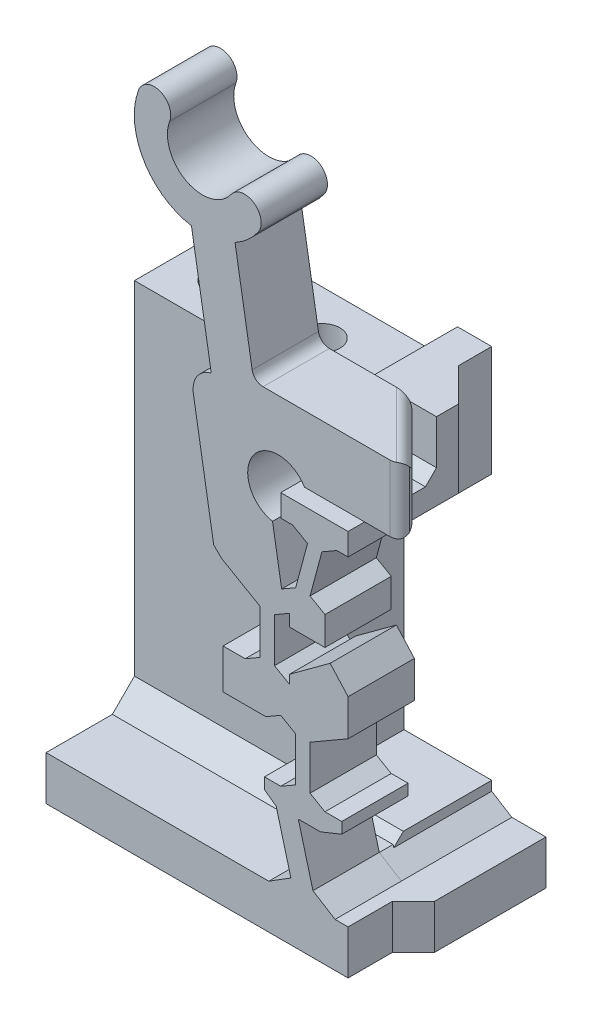
SolidWorks part; units mm, degrees
material "Nylon 6/12"
ref_plane "Front Plane" through (0, 0, 0) normal (0, 0, 1) x (1, 0, 0)
ref_plane "Top Plane" through (0, 0, 0) normal (0, 1, 0) x (1, 0, 0)
ref_plane "Right Plane" through (0, 0, 0) normal (1, 0, 0) x (0, 0, -1)
sketch "Sketch-SkeletonConfigUp" plane through (0, 0, 0) normal (0, 0, 1) x (1, 0, 0)
  line L0 (0, 0) -> (0, -50000) construction
  line L1 (0, 0) -> (4.5811, 6.2164) construction
  line L2 (9.8143, 13.3177) -> (4.5811, 13.945) construction
  line L3 (4.5811, 13.945) -> (2.9713, 10.4094) construction
  line L4 (2.9713, 10.4094) -> (4.5811, 6.2164) construction
  line L5 (4.5811, 13.945) -> (6.2429, 19.1409) construction
  line L6 (2.9713, 10.4094) -> (0.0405, 27.8193) construction
  line L7 (4.5811, 6.2164) -> (9.8143, 13.3177) construction
  line L8 (-587.3593, -797.0242) -> (9.8143, 13.3177) construction
  dimension "D2" = 7.7221
  dimension "D3" = 8.8212
  dimension "D4" = 5.2707
  dimension "D5" = 119.553
  dimension "D6" = 3.8848
  dimension "D7" = 5.4552
  dimension "D8" = 17.6549
  dimension "D9" = 4.4914
  dimension "D10" = 6.745
  dimension "D11" = 145.964
  dimension "D12" = 143.612
sketch "Sketch-SkeletonConfigDown" plane through (0, 0, 0) normal (0, 0, 1) x (1, 0, 0)
  line L0 (0, 0) -> (0, -50000) construction
  line L1 (0, 0) -> (4.5811, 6.2164) construction
  line L2 (9.8143, 13.3177) -> (4.5811, 13.945) construction
  line L3 (4.5811, 13.945) -> (6.1909, 10.4094) construction
  line L4 (6.1909, 10.4094) -> (4.5811, 6.2164) construction
  line L5 (4.5811, 13.945) -> (1.753, 18.6098) construction
  line L6 (6.1909, 10.4094) -> (-8.8652, 19.6294) construction
  line L7 (4.5811, 6.2164) -> (9.8143, 13.3177) construction
  line L8 (-589.9357, -800.5203) -> (9.8143, 13.3177) construction
  dimension "D2" = 7.7221
  dimension "D3" = 8.8212
  dimension "D4" = 5.2707
  dimension "D5" = 119.553
  dimension "D6" = 3.8848
  dimension "D7" = 5.4552
  dimension "D8" = 17.6549
  dimension "D9" = 4.4914
  dimension "D10" = 6.745
  dimension "D11" = 145.964
  dimension "D1" = 143.612
ref_plane "Plane-Cam Base" through (9.128, 0, 0) normal (1, 0, 0) x (0, 0, -1)
ref_plane "Plane-Down-to-Up Derailleur Clearance" through (6.628, 0, 0) normal (1, 0, 0) x (0, 0, -1)
ref_plane "Plane-Cam Cavity Roof" through (5.128, 0, 0) normal (1, 0, 0) x (0, 0, -1)
sketch "Sketch-SwitchBossUp" plane through (0, 0, 0) normal (0, 0, 1) x (1, 0, 0)
  line L0 (3.5811, 11.4759) -> (3.5811, 12.945) construction
  line L5 (5.5811, 12.5552) -> (5.5811, 11.263)
  line L7 (1.5115, 25.1048) -> (2.3566, 20.0847)
  line L8 (-0.4607, 24.7728) -> (0.4359, 19.4465)
  line L9 (2.9713, 10.4094) -> (0.0405, 27.8193) construction
  line L11 (-0.0396, 22.2712) -> (1.9326, 22.6032) construction
  line L15 (6.628, -23.7286) -> (6.628, 23.7286) construction
  line L16 (2.9713, 10.4094) -> (4.5811, 6.2164) construction
  line L17 (3.5811, 12.945) -> (3.5811, 14.945) construction
  line L18 (5.5811, 12.945) -> (5.5811, 14.945) construction
  line L19 (4.2561, 13.945) -> (4.9061, 13.945) construction
  line L20 (3.5811, 14.945) -> (5.5811, 14.945) construction
  line L21 (3.5811, 12.945) -> (5.5811, 12.945) construction
  line L22 (4.5811, 12.945) -> (4.5811, 14.945) construction
  line L23 (4.5811, 6.2164) -> (8.5405, 7.1023) construction
  line L24 (1.9713, 9.4094) -> (1.9713, 11.4094) construction
  line L25 (3.9713, 9.4094) -> (3.9713, 11.4094) construction
  line L26 (3.9713, 9.4094) -> (1.9713, 9.4094) construction
  line L27 (1.9713, 11.4094) -> (3.9713, 11.4094) construction
  line L28 (3.5811, 7.2164) -> (5.5811, 7.2164) construction
  line L29 (3.5811, 7.2164) -> (3.5811, 5.2164) construction
  line L30 (5.5811, 7.2164) -> (5.5811, 5.2164) construction
  line L31 (3.5811, 5.2164) -> (5.5811, 5.2164) construction
  line L32 (4.9061, 6.2164) -> (4.2561, 6.2164) construction
  line L40 (3.2963, 10.4094) -> (2.6463, 10.4094) construction
  line L66 (0.0405, 27.8193) -> (0.0405, 50027.8193) construction
  line L74 (0.5455, 12.7717) -> (-0.3728, 18.2264)
  line L75 (0.3841, 13.7302) -> (2.3564, 14.0622) construction
  line L76 (5.5811, 11.263) -> (5.5811, 12.5552) construction
  line L77 (5.5811, 7.6061) -> (6.628, 8.2105)
  line L80 (5.8152, 10.763) -> (6.628, 9.8603)
  line L81 (9.128, 1033.2419) -> (9.128, 20.0586) construction
  line L82 (4.6532, 17.0847) -> (9.028, 17.0847)
  line L85 (6.9307, 9.5241) -> (8.5405, 7.7363) construction
  line L88 (5.7256, 16.3347) -> (6.628, 16.3347)
  line L92 (3.7762, 8.3129) -> (6.9307, 9.5241) construction
  line L95 (2.3566, 20.0847) -> (7.4359, 20.0847)
  line L96 (7.4359, 20.0847) -> (9.028, 20.0847)
  line L97 (3.2085, 15.0241) -> (3.6203, 12.5779)
  line L98 (1.9713, 9.0197) -> (0.9713, 9.0197)
  line L99 (0.9713, 9.0197) -> (0.9713, 7.2164)
  line L100 (0.9713, 7.2164) -> (2.9061, 7.2164)
  line L101 (4.5811, 6.2164) -> (6.9307, 9.5241) construction
  line L103 (0.0405, 27.8193) -> (1.9448, 26.4638) construction
  line L104 (6.9307, 9.5241) -> (8.5405, 7.7363) construction
  line L107 (1.9713, 9.4094) -> (1.9713, 9.0197) construction
  line L109 (0.0405, 27.8193) -> (-2.1498, 28.6358) construction
  line L111 (6.628, 9.8603) -> (6.628, 8.2105)
  line L112 (6.628, 9.8603) -> (6.9307, 9.5241) construction
  line L113 (2.8424, 4.8267) -> (2.8424, 4.3267)
  line L114 (7.3693, 7.7363) -> (7.3563, 7.7363) construction
  line L121 (5.0383, -1.1653) -> (5.0383, 1.4614) construction
  line L122 (2.8616, 17.0847) -> (3.2085, 15.0241) construction
  line L127 (5.5811, 15.3347) -> (5.5811, 14.945) construction
  line L130 (6.0388, 0.837) -> (6.628, 0.837)
  line L132 (2.8424, 4.3267) -> (3.3749, 3.937)
  line L133 (2.9713, 10.4094) -> (6.1909, 10.4094) construction
  line L134 (4.5811, 10.4094) -> (4.5811, 13.945) construction
  line L135 (4.5811, 10.4094) -> (4.5811, 6.2164) construction
  line L136 (0.8973, 12.4192) -> (0.5455, 12.7717)
  line L137 (3.9713, 9.4094) -> (5.5811, 7.2164) construction
  line L139 (5.8152, 10.763) -> (3.9713, 9.4094)
  line L141 (4.0386, 1.4604) -> (3.0388, 0.8347)
  line L142 (3.0388, 0.8347) -> (3.0388, -1.1653)
  line L143 (9.128, 20.0586) -> (9.128, 18.3333) construction
  line L145 (9.128, 16.6071) -> (9.128, -49992.4167) construction
  line L147 (5.5811, 11.263) -> (5.5811, 12.5552) construction
  line L150 (3.0388, -1.1653) -> (5.0383, -1.1653)
  line L151 (3.3749, 3.937) -> (4.3749, 3.937) construction
  line L152 (4.792, 14.945) -> (4.2561, 12.945)
  line L153 (5.442, 14.945) -> (4.9061, 12.945)
  line L157 (3.5811, 16.3347) -> (3.5811, 15.3347)
  line L158 (6.117, 15.3347) -> (6.628, 15.3347)
  line L162 (3.2963, 11.4094) -> (3.2963, 9.4094)
  line L164 (2.6463, 11.4094) -> (2.6463, 9.4094)
  line L169 (4.2561, 7.2164) -> (4.2561, 5.2164)
  line L170 (4.9061, 5.2164) -> (4.9061, 7.2164)
  line L175 (4.2561, 7.2164) -> (3.5811, 7.6061)
  line L176 (4.9061, 7.2164) -> (5.5811, 7.6061)
  line L177 (5.5811, 7.2164) -> (5.5811, 7.6061) construction
  line L179 (4.2561, 5.2164) -> (3.5811, 4.8267)
  line L180 (3.5811, 5.2164) -> (3.5811, 4.8267) construction
  line L181 (3.5811, 4.8267) -> (2.8424, 4.8267)
  line L183 (4.9061, 5.2164) -> (5.5811, 4.8267)
  line L184 (5.5811, 5.2164) -> (5.5811, 4.8267) construction
  line L186 (9.128, -23.7286) -> (9.128, 23.7286) construction
  line L187 (2.6463, 9.4094) -> (1.9713, 9.0197)
  line L188 (3.2963, 9.4094) -> (3.9713, 9.0197)
  line L189 (3.2963, 11.4094) -> (3.9713, 11.7991)
  line L190 (2.6463, 11.4094) -> (0.8973, 12.4192)
  line L191 (3.9713, 11.4094) -> (3.9713, 11.7991) construction
  line L192 (3.9713, 11.7991) -> (3.9713, 11.263)
  line L193 (4.9061, 12.945) -> (5.5811, 12.5552)
  line L194 (4.2561, 12.945) -> (3.6203, 12.5779)
  line L195 (3.9713, 11.263) -> (5.5811, 11.263)
  line L196 (3.9713, 9.4094) -> (3.9713, 9.0197)
  line L197 (3.5811, 7.2164) -> (3.5811, 7.6061) construction
  line L199 (3.5811, 7.6061) -> (2.9061, 7.2164)
  line L201 (2.8424, 4.3267) -> (2.8424, 3.937) construction
  line L202 (2.8424, 3.937) -> (3.3749, 3.937) construction
  line L204 (5.0383, 1.437) -> (3.0388, 1.437) construction
  line L205 (3.0388, 1.437) -> (3.0388, 0.8347) construction
  line L206 (5.0383, 1.4614) -> (6.0388, 0.837)
  line L207 (9.128, 18.3333) -> (9.128, 16.6071) construction
  line L208 (6.628, -1.1653) -> (6.628, 0.837)
  line L209 (9.128, 20.0586) -> (9.128, 16.6071) construction
  line L211 (5.0383, 1.4614) -> (4.3749, 3.937)
  line L212 (4.0386, 1.4604) -> (3.3749, 3.937)
  line L214 (4.792, 14.945) -> (4.1169, 15.3347)
  line L215 (4.1169, 15.3347) -> (3.5811, 15.3347)
  line L216 (5.442, 14.945) -> (6.117, 15.3347)
  line L217 (5.5811, 12.945) -> (5.5811, 12.5552) construction
  line L218 (5.442, 14.945) -> (5.442, 15.3347) construction
  line L219 (6.117, 15.3347) -> (4.1169, 15.3347) construction
  line L221 (9.028, 17.0847) -> (9.028, 20.0847)
  line L224 (3.5811, 16.3347) -> (5.7256, 16.3347)
  line L232 (6.628, 15.3347) -> (6.628, 16.3347)
  line L233 (6.628, -1.1653) -> (5.0383, -1.1653)
  line L240 (4.3749, 3.937) -> (5.3749, 3.937)
  line L241 (5.3749, 3.937) -> (6.3424, 4.3267)
  line L248 (2.8616, 17.0847) -> (4.6532, 17.0847) construction
  line L367 (5.5811, 4.8267) -> (6.3424, 4.8267)
  line L368 (6.3424, 4.8267) -> (6.3424, 4.3267)
  arc A0 (1.5115, 25.1048) -> (2.5558, 26.0289) centre (0.0405, 27.8193) ccw
  arc A1 (-0.4607, 24.7728) -> (-2.8525, 28.8978) centre (0.0405, 27.8193) cw
  arc A2 (-2.8525, 28.8978) -> (-1.447, 28.3738) centre (-2.1498, 28.6358) cw
  arc A3 (2.5558, 26.0289) -> (1.3338, 26.8987) centre (1.9448, 26.4638) ccw
  arc A4 (-1.447, 28.3738) -> (1.3338, 26.8987) centre (0.0405, 27.8193) ccw
  arc A5 (3.5811, 12.945) -> (3.5811, 14.945) centre (3.1778, 13.945) ccw construction
  arc A6 (5.5811, 12.945) -> (5.5811, 14.945) centre (5.9843, 13.945) cw construction
  arc A7 (2.5293, 9.921) -> (1.9713, 11.4094) centre (1.568, 10.4094) ccw construction
  arc A8 (3.9713, 11.4094) -> (3.9713, 9.4094) centre (4.3745, 10.4094) ccw construction
  arc A9 (3.5811, 7.2164) -> (3.5811, 5.2164) centre (3.1779, 6.2164) cw construction
  arc A10 (5.5811, 7.2164) -> (5.5811, 5.2164) centre (5.9844, 6.2164) ccw construction
  arc A19 (-0.3728, 18.2264) -> (0.4359, 19.4465) centre (0.6836, 18.4042) cw
  circle A28 centre (0.0405, 27.8193) radius 2.3375 construction
  arc A29 (1.9713, 9.4094) -> (2.5293, 9.921) centre (1.568, 10.4094) ccw construction
  arc A37 (3.2085, 15.0241) -> (4.6532, 17.0847) centre (3.4651, 16.381) cw
  point P53 (4.5811, 13.945)
  point P63 (2.9713, 10.4094)
  point P93 (0.9465, 22.4372)
  dimension "D23" = 1.5875
  dimension "D24" = 0.75
  dimension "D2" = 2
  dimension "D5" = 2
  dimension "D6" = 0.65
  dimension "D8" = 42
  dimension "D16" = 42
  dimension "D27" = 120
  dimension "D28" = 120
  dimension "D29" = 120
  dimension "D30" = 120
  dimension "D31" = 120
  dimension "D32" = 120
  dimension "D33" = 120
  dimension "D34" = 120
  dimension "D17" = 0.5
  dimension "D21" = 1
  dimension "D9" = 17.5
  dimension "D22" = 1
  dimension "D38" = 2
  dimension "D39" = 0.5
  dimension "D40" = 60
  dimension "D41" = 1
  dimension "D42" = 45
  dimension "D43" = 120
  dimension "D10" = 15
  dimension "D12" = 2.5
  dimension "D13" = 1
  dimension "D19" = 1
  dimension "D25" = 15
  dimension "D26" = 120
  dimension "D35" = 120
  dimension "D20" = 3
  dimension "D48" = 2
  dimension "D49" = 0.6
  dimension "D7" = 0.75
  dimension "D14" = 3
  dimension "D82" = 1
  dimension "D83" = 3.5
extrude "Boss-Switch Body" add sketch "Sketch-SwitchBossUp" along normal blind 3
sketch "Sketch1" plane through (0, 0, 0) normal (0, 0, -1) x (-1, 0, 0)
  line L1 (-7.5811, -1.1653) -> (0.4122, -1.1653)
  line L2 (-7.5811, -1.1653) -> (-7.5811, 0.837)
  line L4 (0.4122, -1.1653) -> (0.4122, 0.8347)
  line L5 (-3.5811, 18.8347) -> (-7.5811, 18.8347)
  line L10 (-7.5811, 18.8347) -> (-7.5811, 15.3347)
  line L11 (-4.0386, 1.4604) -> (-5.0386, 1.4604)
  line L12 (-7.5811, 15.3347) -> (-3.5811, 15.3347)
  line L13 (-4.0386, 1.4604) -> (-3.0388, 0.8347)
  line L14 (-3.5811, 15.3347) -> (-3.5811, 18.8347)
  line L20 (-4.3749, 3.937) -> (-5.0383, 1.4614) construction
  line L22 (-3.0388, -1.1653) -> (-6.628, -1.1653) construction
  line L23 (-3.0388, 0.8347) -> (0.4122, 0.8347)
  line L24 (-5.0386, 1.4604) -> (-6.0388, 0.837)
  line L25 (-6.0388, 0.837) -> (-7.5811, 0.837)
  point P5 (-3.5811, 15.3347)
  dimension "D1" = 3.5
extrude "Boss-Flange Width" add sketch "Sketch1" along normal blind 5
ref_plane "Plane-Sta2Sit Groove" through (0.0405, 0, 0) normal (1, 0, 0) x (0, 0, -1)
ref_plane "Plane-Cam Outer Surface" through (-12.0395, 0, 0) normal (1, 0, 0) x (0, 0, -1)
ref_plane "Plane-FlangeTop" through (-7.0395, 0, 0) normal (1, 0, 0) x (0, 0, -1)
sketch "Sketch2" plane through (-7.0395, 0, 0) normal (1, 0, 0) x (0, 0, -1)
  line L0 (5, 15.3347) -> (-3, 15.3347) construction
  line L1 (5, 17.3347) -> (1, 17.3347)
  line L2 (5, 17.3347) -> (5, 15.3347)
  line L3 (5, 15.3347) -> (1, 15.3347)
  line L4 (1, 17.3347) -> (1, 15.3347)
  line L5 (-3, -1.1653) -> (-3, 0.837) construction
  line L11 (5, 0.8347) -> (-3, 0.8347)
  line L12 (5, 0.8347) -> (5, -1.1653)
  line L13 (5, -1.1653) -> (-3, -1.1653)
  line L14 (-3, 0.8347) -> (-3, -1.1653)
  line L15 (0, 10.4094) -> (0, 27.8193) construction
  line L17 (5, 0.837) -> (5, -1.1653) construction
  line L18 (-3, 0.8347) -> (0, 0.8347) construction
  dimension "D1" = 1
  dimension "D2" = 2
extrude "Boss-Flange Height" add sketch "Sketch2" along normal up to surface (11.6675 mm away)
sketch "Sketch24" plane through (0, 0, 0) normal (0, 0, 1) x (1, 0, 0)
  line L0 (3.5811, 16.3347) -> (7.5811, 16.3347)
  line L1 (7.5811, 17.0847) -> (7.5811, 15.3347) construction
  line L2 (3.5811, 16.3347) -> (3.5811, 18.8347)
  line L3 (3.5811, 18.8347) -> (7.5811, 18.8347)
  line L4 (7.5811, 18.8347) -> (7.5811, 16.3347)
  point P5 (7.5811, 18.8347)
extrude "Cut-Wall Clearance" cut sketch "Sketch24" against normal up to surface (1 mm away) up to face at (-1.7292, 16.3347, -1)
sketch "Sketch10" plane through (0, 15.3347, 0) normal (0, 1, 0) x (1, 0, 0)
  line L0 (9.128, -23.7286) -> (9.128, 23.7286) construction
  line L1 (7.5811, 5) -> (5.128, 5)
  line L2 (7.5811, 5) -> (7.5811, 2)
  line L3 (7.5811, 2) -> (5.128, 2)
  line L5 (4.628, 7) -> (4.628, 1) construction
  line L6 (3.5811, 1) -> (-7.0395, 1) construction
  line L8 (5.128, 5) -> (5.128, 2)
  dimension "D1" = 1
  dimension "D2" = 0.5
  dimension "D3" = 4.5
extrude "Cut-Up-To-Down Derailleur Clearance" cut sketch "Sketch10" along normal up to next
sketch "Sketch17" plane through (0, 15.3347, 0) normal (0, -1, 0) x (1, 0, 0)
  line L0 (5.128, -5) -> (-7.0395, -5)
  line L1 (5.128, -5) -> (-7.0395, -5) construction
  line L2 (-7.0395, -5) -> (-7.0395, -1)
  line L3 (-7.0395, -1) -> (5.128, -1)
  line L4 (5.128, -1) -> (5.128, -5)
  line L5 (-7.0395, -1) -> (-7.0395, -5) construction
extrude "Boss-Flange Support" add sketch "Sketch17" along normal up to surface (14.5 mm away) up to face at (-2.0003, 0.8347, -1)
sketch "Sketch-HolePositions" plane through (0, -1.1653, 0) normal (0, -1, 0) x (1, 0, 0)
  line L0 (-7.0395, -3) -> (7.5811, -3) construction
  line L1 (7.5811, -5) -> (-7.0395, -5) construction
  line L2 (7.5811, -5) -> (7.5811, 0) construction
  line L4 (-7.0395, -22.2167) -> (-7.0395, 22.2167) construction
  point P6 (-5.0395, -3)
  point P7 (-0.5395, -3)
  dimension "D1" = 2
  dimension "D2" = 4.5
  dimension "D3" = 2
sketch "Sketch6" plane through (0, -1.1653, 0) normal (0, -1, 0) x (-1, 0, 0)
  point P0 (5.0395, 3)
  point P3 (0.5395, 3)
hole_wizard "Tap Drill for M2x0.4 Tap1" positions "Sketch6" profile "Sketch5" hole size "M2x0.4" standard "ANSI Metric" end condition through all
sketch "Sketch5" plane through (-5.0395, -1.1653, -3) normal (1, 0, 0) x (0, 0, -1)
  line L0 (0, 0) -> (0, 30.5511)
  line L1 (0, 30.5511) -> (0.8, 30.5511)
  line L2 (0.8, 30.5511) -> (0.8, 0)
  line L5 (0.8, 0) -> (0, 0)
  line L11 (0, -6.35) -> (0, 107.95) construction
  dimension "Thru Hole Dia." = 1.6
  dimension "Thru Hole Depth" = 30.5511
sketch "Sketch9" plane through (0, -1.1653, 0) normal (0, -1, 0) x (1, 0, 0)
  point P0 (-5.0395, -3)
  point P3 (-0.5395, -3)
hole_wizard "M2 Clearance Hole2" positions "Sketch9" profile "Sketch8" hole size "M2" standard "ANSI Metric"
sketch "Sketch8" plane through (-5.0395, -1.1653, -3) normal (1, 0, 0) x (0, 0, -1)
  line L0 (0, 0) -> (0, 15.721)
  line L1 (0, 15.721) -> (1.2, 15)
  line L2 (1.2, 15) -> (1.2, 0)
  line L5 (1.2, 0) -> (0, 0)
  line L10 (0, 15.721) -> (-1.2, 15) construction
  line L11 (0, -6.35) -> (0, 107.95) construction
  dimension "Hole Dia." = 2.4
  dimension "Hole Depth" = 15
  dimension "Drill Angle" = 118
sketch "Sketch-Measurements for Derailleur Ramps" [suppressed] plane through (0, 0, 0) normal (0, 0, 1) x (1, 0, 0)
  line L0 (3.184, 15.1695) -> (2.4687, 19.4188)
  line L1 (2.8264, 17.2941) -> (1.8402, 17.1281)
  line L2 (2.9713, 10.4094) -> (0.0405, 27.8193) construction
  line L3 (1.8402, 17.1281) -> (-1.3081, 15.0016)
  line L4 (6.1909, 10.4094) -> (-8.8652, 19.6294) construction
  line L5 (1.8402, 17.1281) -> (2.6012, 12.6077)
  line L6 (2.6012, 12.6077) -> (-1.3081, 15.0016)
  line L7 (0.2661, 16.0649) -> (0.2661, 17.1281)
  line L8 (0.2661, 17.1281) -> (1.8402, 17.1281)
  line L9 (6.1909, 10.4094) -> (2.9713, 10.4094)
  line L10 (5.386, 8.3129) -> (3.7762, 8.3129)
  line L11 (2.6116, 18.5698) -> (1.5115, 25.1048) construction
  line L12 (6.1909, 10.4094) -> (4.5811, 6.2164) construction
  line L13 (4.5811, 8.3129) -> (4.5811, 8.7912)
  line L14 (4.5811, 6.2164) -> (5.386, 8.3129)
  line L15 (2.9713, 10.4094) -> (4.5811, 6.2164) construction
  line L16 (3.7762, 8.3129) -> (4.5811, 6.2164)
  line L17 (5.386, 8.3129) -> (5.386, 8.7912)
  dimension "D1" = 1.5742
  dimension "D2" = 0.8049
sketch "Sketch12" plane through (0, 20.0847, 0) normal (0, 1, 0) x (1, 0, 0)
  line L0 (6.528, 0) -> (9.028, -2.5)
  line L1 (9.028, -2.5) -> (9.028, 0)
  line L2 (9.028, 0) -> (6.528, 0)
  line L3 (9.028, -3) -> (9.028, 0) construction
  line L6 (9.028, 0) -> (2.3566, 0) construction
  point P1 (0, 0)
  point P6 (0, 0)
  dimension "D1" = 45
extrude "Cut-Up-to-Down Cantilever Slope" cut sketch "Sketch12" against normal up to next
ref_plane "Plane1" through (0, 7.1023, 0) normal (0, 1, 0) x (1, 0, 0)
ref_plane "Plane-Cantilever Cut" [suppressed] through (7.0848, 8.5204, -1.9058) normal (-0.6301, -0.7578, 0.1695) x (-0.7765, 0.6151, -0.1368)
sketch "Sketch14" [suppressed] plane through (7.0848, 8.5204, -1.9058) normal (-0.6301, -0.7578, 0.1695) x (-0.7765, 0.6151, -0.1368)
  line L0 (2.3023, -1.6911) -> (-0.3551, -1.6911)
  line L2 (2.3023, -4.3362) -> (2.3023, -1.6911)
  line L3 (-0.3551, -1.6911) -> (-0.3551, -4.4608)
  line L5 (-0.3551, -4.4608) -> (1.0087, -5.0843)
  line L6 (1.0087, -5.0843) -> (2.3023, -4.3362)
extrude "Cut-Down-to-Up Cantilever Slope" [suppressed] cut sketch "Sketch14" against normal up to next
ref_plane "Plane-Symmetry Plane" through (0, 0, 1.5) normal (0, 0, 1) x (1, 0, 0)
sketch "Sketch-Cable Center Point" plane through (0, 0, 1.5) normal (0, 0, 1) x (1, 0, 0)
  line L0 (0.0405, 27.8193) -> (0.1722, 27.0366)
  line L1 (2.9713, 10.4094) -> (0.0405, 27.8193) construction
  point P0 (0.0405, 27.8193)
  dimension "D1" = 0.7937
chamfer "Chamfer-Flange Support" distance 1.5 angle 45 1 edges at (3.5811, 17.3347, -3)
chamfer "Chamfer-Flange Support 2" distance 1.5 angle 45 2 edges at (5.128, 17.0847, -2) (5.128, 15.3347, -1.5)
chamfer "Chamfer-Flange Support 3" distance 1 angle 45 1 edges at (-2.0003, 0.8347, -1)
chamfer "Chamfer3" distance 0.5 angle 45 3 edges at (3.5811, 15.8347, -1) (5.1045, 15.3347, -1) (5.5811, 16.3347, -1)
chamfer "Chamfer7" [suppressed] distance 1 angle 45
sketch "Sketch23" plane through (0, 0, -1) normal (0, 0, 1) x (1, 0, 0)
  line L0 (5.128, 1.8347) -> (1.1605, 1.8347)
  line L1 (-7.0395, 1.8347) -> (5.128, 1.8347) construction
  line L2 (1.1605, 1.8347) -> (1.1605, 13.8347)
  line L3 (1.1605, 13.8347) -> (5.128, 13.8347)
  line L4 (5.128, 13.8347) -> (5.128, 1.8347)
  line L5 (0.6605, -1.1653) -> (0.6605, 13.8347) construction
  dimension "D1" = 0.5
extrude "Cut-Gap for Printing" cut sketch "Sketch23" against normal through all
sketch "Sketch25" plane through (0, 0, 0) normal (0, 0, 1) x (1, 0, 0)
  line L0 (6.628, 15.3347) -> (7.5811, 15.3347)
  line L1 (7.5811, 15.3347) -> (7.5811, 18.8347)
  line L2 (7.5811, 18.8347) -> (6.628, 18.8347)
  line L3 (6.628, -23.7286) -> (6.628, 23.7286) construction
  line L4 (7.5811, 18.8347) -> (3.5811, 18.8347) construction
  line L5 (6.628, 18.8347) -> (6.628, 15.3347)
extrude "Cut-Derailleur Clearance" cut sketch "Sketch25" against normal through all
chamfer "Chamfer8" distance 1 angle 45 1 edges at (6.628, -0.1641, 0)
fillet "Fillet1" radius 0.5 5 edges at (6.528, 18.5847, 0) (9.028, 18.5847, 3) (7.778, 20.0847, 1.25) (9.028, 18.5847, 2.5) (7.778, 17.0847, 1.25)
fillet "Fillet2" radius 0.5 1 edges at (2.3566, 20.0847, 1.5)
equation "\"axle-diameter\"=2"
equation "\"switch-thickness\"=12"
equation "\"base-width\"=4.0"
equation "\"axle-bushing-radius\"=3"
equation "\"clearance\"= 0.25"
equation "\"arm-width\"=1.5"
equation "\"min-diameter\"=70"
equation "\"alpha\"=143.6120"
equation "\"gamma\"=119.5526"
equation "\"delta\"=145.9637"
equation "\"epsilon\"=6.7452"
equation "\"l_AB\"=8.8212"
equation "\"l_AC\"=4.4914"
equation "\"l_BD\"=5.2707"
equation "\"l_CD\"=3.8848"
equation "\"l_CE\"=17.6549"
equation "\"l_DF\"=5.4552"
equation "\"l_OA\"=7.7221"
equation "\"D2@Sketch-SkeletonConfigUp\" = \"l_OA\""
equation "\"D3@Sketch-SkeletonConfigUp\" = \"l_AB\""
equation "\"D4@Sketch-SkeletonConfigUp\" = \"l_BD\""
equation "\"D5@Sketch-SkeletonConfigUp\" = \"gamma\""
equation "\"D6@Sketch-SkeletonConfigUp\" = \"l_CD\""
equation "\"D7@Sketch-SkeletonConfigUp\" = \"l_DF\""
equation "\"D8@Sketch-SkeletonConfigUp\" = \"l_CE\""
equation "\"D9@Sketch-SkeletonConfigUp\" = \"l_AC\""
equation "\"D_groove\"=3.175"
equation "\"D7@Sketch-SkeletonConfigDown\" = \"l_DF\""
equation "\"D6@Sketch-SkeletonConfigDown\" = \"l_CD\""
equation "\"D2@Sketch-SkeletonConfigDown\" = \"l_OA\""
equation "\"D3@Sketch-SkeletonConfigDown\" = \"l_AB\""
equation "\"D9@Sketch-SkeletonConfigDown\" = \"l_AC\""
equation "\"D8@Sketch-SkeletonConfigDown\" = \"l_CE\""
equation "\"D5@Sketch-SkeletonConfigDown\" = \"gamma\""
equation "\"D4@Sketch-SkeletonConfigDown\" = \"l_BD\""
equation "\"D1@Sketch-SkeletonConfigDown\" = \"alpha\""
equation "\"hinge_length\"=1.5"
equation "\"hinge_depth\"=0.25"
equation "\"D10@Sketch-SkeletonConfigUp\"=\"epsilon\""
equation "\"D11@Sketch-SkeletonConfigUp\"=\"delta\""
equation "\"D12@Sketch-SkeletonConfigUp\"=\"alpha\""
equation "\"D11@Sketch-SkeletonConfigDown\"=\"delta\""
equation "\"D10@Sketch-SkeletonConfigDown\"=\"epsilon\""
equation "\"EE_dx\"=8.9056"
equation "\"EE_dy\"=8.1898"
equation "\"r_groove\"=\"D_groove\"/2"
equation "\"t_wall\"=25.4/16"
equation "\"width_lower\"=\"D_groove\"+\"t_wall\""
equation "\"cable_to_bottom\"=30.6257"
equation "\"switch_EE-up_base_dy\"=24"
equation "\"switch_EE-down_base_dy\"=16"
equation "\"D_axle\"=25.4/8"
equation "\"D_up_to_down\"=16"
equation "\"D_down_to_up\"=25"
equation "\"t_cam_base\"=7.5"
equation "\"D23@Sketch-SwitchBossUp\"=\"D_groove\"/2"
equation "\"D1@Sketch-Cable Center Point\"=\"D_groove\"/4"
